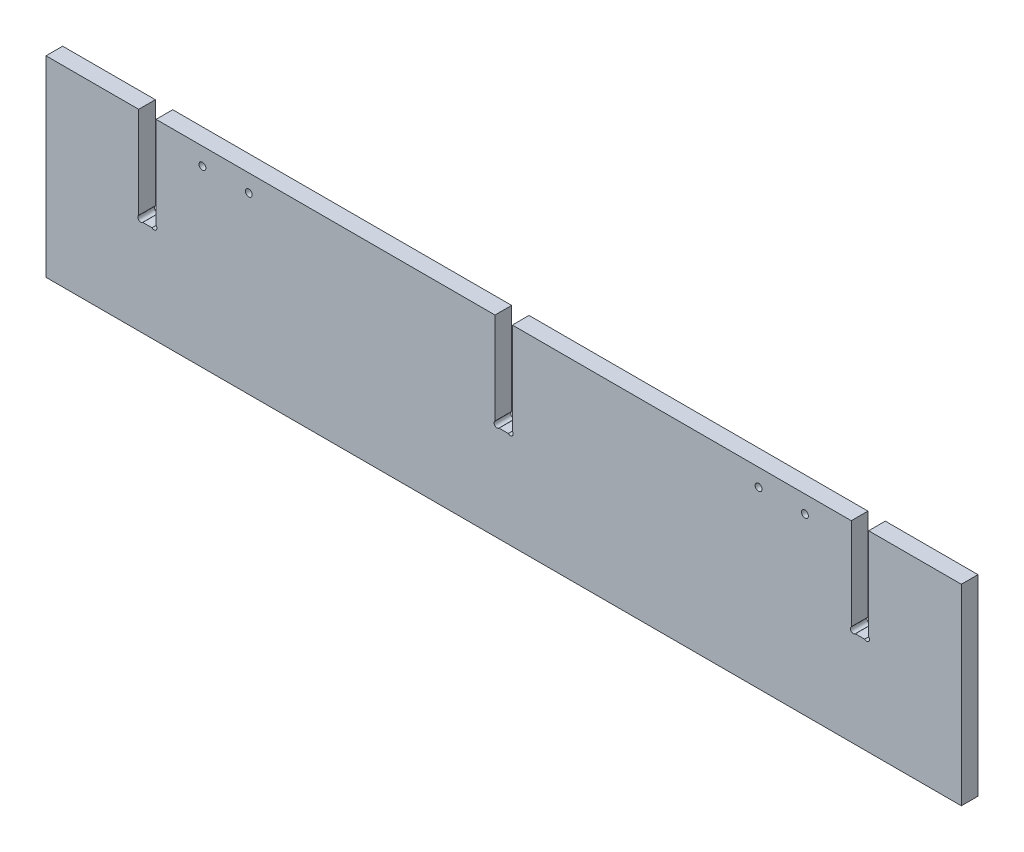
SolidWorks part; units mm, degrees
material "Pine"
ref_plane "Front Plane" through (0, 0, 0) normal (0, 0, 1) x (1, 0, 0)
ref_plane "Top Plane" through (0, 0, 0) normal (0, 1, 0) x (1, 0, 0)
ref_plane "Right Plane" through (0, 0, 0) normal (1, 0, 0) x (0, 0, -1)
sketch "Sketch1" plane through (0, 0, 0) normal (0, 0, 1) x (1, 0, 0)
  line L1 (-343.9704, 239.5731) -> (659.3296, 239.5731)
  line L2 (-343.9704, 239.5731) -> (-343.9704, 29.2294)
  line L3 (-343.9704, 29.2294) -> (659.3296, 29.2294)
  line L4 (659.3296, 239.5731) -> (659.3296, 29.2294)
  dimension "D1" = 1003.3
  dimension "D2" = 210.3438
extrude "Boss-Extrude1" add sketch "Sketch1" along normal blind 18.2562
sketch "Sketch2" plane through (0, 0, 18.2562) normal (0, 0, 1) x (1, 0, 0)
  line L0 (-343.9704, 239.5731) -> (-242.3704, 239.5731) construction
  line L1 (659.3296, 239.5731) -> (-343.9704, 239.5731) construction
  line L6 (157.6796, 239.5731) -> (148.1546, 239.5731) construction
  line L15 (659.3296, 239.5731) -> (557.7296, 239.5731) construction
  line L16 (557.7296, 239.5731) -> (557.7296, 138.9073)
  line L17 (553.2394, 134.4171) -> (543.1697, 134.4171)
  line L18 (557.7296, 239.5731) -> (538.6796, 239.5731)
  line L19 (538.6796, 239.5731) -> (538.6796, 138.9073)
  line L23 (157.6796, 239.5731) -> (157.6796, 196.9171) construction
  line L24 (-242.3704, 239.5731) -> (-223.3204, 239.5731)
  line L25 (-242.3704, 239.5731) -> (-242.3704, 138.9073)
  line L26 (-237.8803, 134.4171) -> (-227.8106, 134.4171)
  line L27 (-223.3204, 239.5731) -> (-223.3204, 138.9073)
  line L28 (148.1546, 239.5731) -> (167.2046, 239.5731)
  line L29 (148.1546, 239.5731) -> (148.1546, 138.9073)
  line L30 (152.6447, 134.4171) -> (162.7144, 134.4171)
  line L31 (167.2046, 239.5731) -> (167.2046, 138.9073)
  arc A6 (-242.3704, 138.9073) -> (-237.8803, 134.4171) centre (-240.1254, 136.6622) ccw
  arc A7 (-227.8106, 134.4171) -> (-223.3204, 138.9073) centre (-225.5655, 136.6622) ccw
  arc A8 (148.1546, 138.9073) -> (152.6447, 134.4171) centre (150.3996, 136.6622) ccw
  arc A9 (162.7144, 134.4171) -> (167.2046, 138.9073) centre (164.9595, 136.6622) ccw
  arc A10 (553.2394, 134.4171) -> (557.7296, 138.9073) centre (555.4845, 136.6622) ccw
  arc A11 (538.6796, 138.9073) -> (543.1697, 134.4171) centre (540.9246, 136.6622) ccw
  point P6 (-232.8454, 239.5731)
  dimension "D1" = 101.6
  dimension "D2" = 105.156
  dimension "D3" = 19.05
  dimension "D4" = 9.525
  dimension "D5" = 19.05
  dimension "D6" = 101.6
  dimension "D7" = 19.05
  dimension "D8" = 105.156
  dimension "D9" = 105.156
  dimension "D10" = 19.05
extrude "Cut-Extrude1" cut sketch "Sketch2" against normal blind 18.2562 contours L29 A8 L30 A9 L31 L28
extrude "Cut-Extrude2" cut sketch "Sketch2<4>" against normal blind 18.2562 contours L19 A11 L17 A10 L16 L18
sketch "Sketch2<4>" plane through (0, 0, 18.2562) normal (0, 0, 1) x (1, 0, 0) same geometry as "Sketch2"
extrude "Cut-Extrude3" cut sketch "Sketch2<5>" against normal blind 18.2562 contours L25 A6 L26 A7 L27 L24
sketch "Sketch2<5>" plane through (0, 0, 18.2562) normal (0, 0, 1) x (1, 0, 0) same geometry as "Sketch2"
hole_wizard "19/64 (0.29688) Diameter Hole1" positions "3DSketch1" profile "Sketch3" hole size "19/64" standard "ANSI Inch" end condition through all
sketch3d "3DSketch1"
  line L0 (-223.3204, 239.5731, 18.2562) -> (-223.3204, 138.9073, 18.2562) construction
  line L1 (148.1546, 239.5731, 18.2562) -> (-223.3204, 239.5731, 18.2562) construction
  line L2 (538.6796, 239.5731, 18.2562) -> (167.2046, 239.5731, 18.2562) construction
  line L3 (538.6796, 239.5731, 18.2562) -> (538.6796, 138.9073, 18.2562) construction
  point P0 (487.8796, 220.5231, 18.2562)
  point P2 (437.0796, 220.5231, 18.2562)
  point P4 (-172.5204, 220.5231, 18.2562)
  point P6 (-121.7204, 220.5231, 18.2562)
  dimension "D1" = 50.8
  dimension "D2" = 19.05
  dimension "D3" = 19.05
  dimension "D4" = 50.8
  dimension "D5" = 19.05
  dimension "D6" = 19.05
  dimension "D7" = 50.8
  dimension "D8" = 50.8
sketch "Sketch3" plane through (487.8796, 220.5231, 18.2562) normal (1, 0, 0) x (0, -1, 0)
  line L0 (0, 0) -> (0, 18.2562)
  line L1 (0, 18.2562) -> (3.7704, 18.2562)
  line L2 (3.7704, 18.2562) -> (3.7704, 0)
  line L5 (3.7704, 0) -> (0, 0)
  line L11 (0, -6.35) -> (0, 107.95) construction
  dimension "Thru Hole Dia." = 7.5408
  dimension "Thru Hole Depth" = 18.2562
